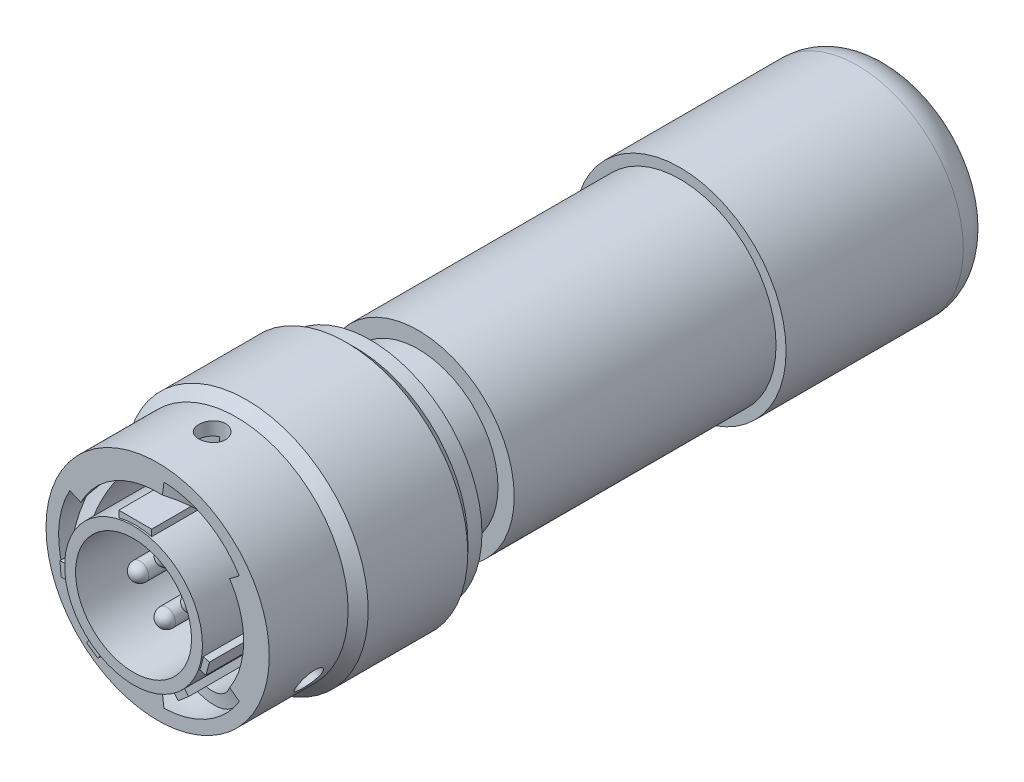
SolidWorks part; units mm, degrees
ref_plane "Front Plane" through (0, 0, 0) normal (0, 0, 1) x (1, 0, 0)
ref_plane "Top Plane" through (0, 0, 0) normal (0, 1, 0) x (1, 0, 0)
ref_plane "Right Plane" through (0, 0, 0) normal (1, 0, 0) x (0, 0, -1)
sketch "Sketch1" plane through (0, 0, 0) normal (1, 0, 0) x (0, 0, -1)
  line L0 (0, 0) -> (68, 0) construction
  line L1 (0, 10.9) -> (0, -10.9) construction
  line L2 (25.5, 8.6) -> (25.5, -8.6) construction
  line L3 (68, 9.5) -> (68, -9.5) construction
  line L4 (0, 7.7089) -> (0, -7.7089) construction
  line L6 (0, 5.1943) -> (0, -5.1943) construction
  line L7 (0, 6.1722) -> (0, -6.1722) construction
  line L8 (7.9502, 5.1435) -> (7.9502, -5.1435) construction
  line L10 (0, 10) -> (0, -10) construction
  line L13 (0, 0) -> (7.9502, 0) construction
  line L14 (32.5, 7.1437) -> (32.5, -7.1437) construction
  line L15 (9.2202, 6.7437) -> (9.2202, -6.7437) construction
  line L16 (0, 8.9154) -> (0, -8.9154) construction
  line L17 (32.5, 7.1437) -> (31.4417, 7.1438) construction
  point P12 (0.1524, 0)
  point P14 (7.9502, 0)
  point P21 (2.159, 0)
  point P22 (5.842, 0)
  point P25 (30.722, 0)
  point P29 (25.5, 0)
  point P30 (23.356, 0)
  point P34 (32.5, 0)
  point P42 (9.2202, 0)
  dimension "D1" = 7.366
  dimension "OAL" = 68
  dimension "D2" = 1.778
  dimension "Q" = 21.8
  dimension "Y" = 12.3444
  dimension "Z" = 10.3886
  dimension "P" = 10.287
  dimension "D" = 2.159
  dimension "W" = 15.4178
  dimension "B-Thread" = 14.2875
  dimension "B-Pitch" = 1.0583
  dimension "L" = 32.5
  dimension "N" = 9.2202
  dimension "X" = 13.4874
  dimension "V" = 17.8308
  dimension "F" = 1.27
  dimension "E" = 3.3782
  dimension "M" = 9.0678
  dimension "Nut OD" = 19
  dimension "Body Lg" = 42.5
  dimension "Body OD" = 17.2
  dimension "Q2" = 20
sketch "Sketch2" plane through (0, 0, 0) normal (0, 0, 1) x (1, 0, 0)
  circle A0 centre (0, 0) radius 6.1722 construction
  circle A1 centre (0, 0) radius 6.7437 construction
  circle A2 centre (0, 0) radius 10.9 construction
  circle A3 centre (0, 0) radius 8.9154 construction
sketch "Sketch3" plane through (0, 0, 0) normal (1, 0, 0) x (0, 0, -1)
  line L0 (0, 0) -> (68, 0) construction
  line L1 (9.7282, 6.7437) -> (9.7282, 6.0854)
  line L2 (0, 6.1722) -> (9.2202, 6.1722)
  line L3 (0, 6.1722) -> (0, 5.1943)
  line L4 (0, 5.1943) -> (32.5, 5.1943)
  line L5 (19.8, 6.0854) -> (20.8583, 7.1438)
  line L6 (9.7282, 6.0854) -> (19.8, 6.0854)
  line L7 (7.9502, 5.1435) -> (30.722, 5.1435)
  line L8 (7.9502, 5.1435) -> (7.9502, 0)
  line L9 (7.9502, 0) -> (30.722, 0)
  line L10 (30.722, 5.1435) -> (30.722, 0)
  line L11 (20.8583, 7.1438) -> (31.4417, 7.1438)
  line L12 (31.4417, 7.1438) -> (32.5, 6.0854)
  line L13 (31.4417, 7.1438) -> (32.5, 7.1437) construction
  line L14 (32.5, 7.1437) -> (32.5, 6.0854) construction
  line L15 (19.8, 6.0854) -> (19.8, 7.1438) construction
  line L16 (19.8, 7.1438) -> (20.8583, 7.1438) construction
  line L26 (32.5, 6.0854) -> (32.5, 5.1943)
  line L31 (9.7282, 6.7437) -> (9.2202, 6.7437)
  line L35 (9.2202, 6.7437) -> (9.2202, 6.1722)
  dimension "D1" = 12.7
  dimension "D2" = 0.508
revolve "Revolve1" add sketch "Sketch3" angle 360 about L0
sketch "Sketch4" plane through (0, 0, 0) normal (0, 0, 1) x (1, 0, 0)
  line L0 (-1.4732, 6.5808) -> (1.4732, 6.5808)
  line L1 (0, 6.5808) -> (0, 0) construction
  line L2 (0, 0) -> (6.4872, -1.7383) construction
  line L3 (0, 0) -> (4.317, -5.1448) construction
  line L4 (0, 0) -> (-3.8522, -5.5015) construction
  line L5 (0, 0) -> (-6.6905, -0.5853) construction
  line L6 (6.645, -1.1494) -> (6.3295, -2.3271)
  line L7 (4.784, -4.753) -> (3.85, -5.5367)
  line L8 (-3.3528, -5.8512) -> (-4.3515, -5.1518)
  line L9 (-6.6374, -1.1926) -> (-6.7437, 0.0219)
  line L10 (6.645, -1.1494) -> (6.0905, -1.0008)
  line L11 (6.3295, -2.3271) -> (5.775, -2.1785)
  line L12 (4.784, -4.753) -> (4.415, -4.3132)
  line L13 (3.85, -5.5367) -> (3.481, -5.0969)
  line L14 (-3.3528, -5.8512) -> (-3.0236, -5.3809)
  line L15 (-4.3515, -5.1518) -> (-4.0223, -4.6816)
  line L16 (-6.6374, -1.1926) -> (-6.0655, -1.1426)
  line L17 (-6.7437, 0.0219) -> (-6.1718, 0.072)
  line L18 (-1.4732, 6.5808) -> (-1.4732, 5.9938)
  line L19 (1.4732, 6.5808) -> (1.4732, 5.9938)
  arc A0 (3.481, -5.0969) -> (4.415, -4.3132) centre (0, 0) ccw
  arc A1 (5.775, -2.1785) -> (6.0905, -1.0008) centre (0, 0) ccw
  circle A2 centre (0, 0) radius 6.1722 construction
  circle A3 centre (0, 0) radius 6.7437 construction
  arc A4 (-4.0223, -4.6816) -> (-3.0236, -5.3809) centre (0, 0) ccw
  circle A5 centre (0, 0) radius 6.7437 construction
  arc A6 (-6.1718, 0.072) -> (-6.0655, -1.1426) centre (0, 0) ccw
  arc A7 (1.4732, 5.9938) -> (-1.4732, 5.9938) centre (0, 0) ccw
  dimension "D1" = 2.9464
  dimension "D2" = 105
  dimension "D3" = 140
  dimension "D4" = 215
  dimension "D5" = 265
  dimension "D6" = 1.2192
extrude "Boss-Extrude1" add sketch "Sketch4" against normal up to vertex (9.2202 mm away) from vertex up to point (0, 0, -9.2202) starting at point (0, 0, -0.1524)
sketch "Sketch5" plane through (0, 0, 0) normal (1, 0, 0) x (0, 0, -1)
  line L0 (32.5, 0) -> (0, 0) construction
  line L1 (2.159, 10) -> (2.159, 7.7089)
  line L3 (17.399, 7.7089) -> (17.399, 8.9789)
  line L4 (17.399, 8.9789) -> (21.209, 8.9789)
  line L5 (21.209, 8.9789) -> (21.209, 10)
  line L6 (2.159, 7.7089) -> (17.399, 7.7089)
  line L7 (2.159, 10) -> (9.2202, 10)
  line L8 (21.209, 10) -> (19.939, 10)
  line L9 (19.939, 10) -> (19.039, 10.9)
  line L10 (19.039, 10.9) -> (10.1202, 10.9)
  line L11 (10.1202, 10.9) -> (9.2202, 10)
  dimension "D2" = 1.27
  dimension "D5" = 45
  dimension "D1" = 3.81
  dimension "D3" = 19.05
  dimension "D4" = 45
  dimension "D6" = 1.27
revolve "Revolve2" add sketch "Sketch5" angle 360 about L0
sketch "Sketch6" plane through (0, 0, 0) normal (0, 1, 0) x (1, 0, 0)
  line L0 (0, 0) -> (0, 68) construction
  circle A0 centre (0, 7.0358) radius 1.1938
  dimension "D1" = 2.3876
extrude "Cut-Extrude1" cut sketch "Sketch6" along normal through all
sketch "Sketch7" plane through (0, 0, -2.159) normal (0, 0, 1) x (1, 0, 0)
  circle A0 centre (0, 0) radius 7.7089 construction
  circle A1 centre (0, 0) radius 7.7089
  point P3 (-7.7089, 0)
curve "Helix/Spiral1" pitch 19.5072 height 4.8768 radius 7.7089 centre (0, 0, -2.159) axis (0, 0, -1) start towards (1, 0, 0)
ref_plane "Plane2" through (-7.7089, 0, -2.159) normal (0, 0.9276, -0.3736) x (-1, 0, 0)
sketch "Sketch8" plane through (-7.7089, 0, -2.159) normal (0, 0.9276, -0.3736) x (-1, 0, 0)
  line L0 (-7.7089, 0) -> (0, 0) construction
  line L1 (0, 0) -> (1.164, 0) construction
  line L2 (-0.1185, 1.3462) -> (1.0613, 1.3462)
  line L3 (1.164, 0) -> (1.164, 2.3275) construction
  line L4 (-0.1185, -1.3462) -> (1.0613, -1.3462)
  arc A0 (1.0613, -1.3462) -> (1.0613, 1.3462) centre (-7.7089, 0) ccw
  arc A1 (-0.1185, -1.3462) -> (-0.1185, 1.3462) centre (-7.7089, 0) ccw
  dimension "GG" = 2.6924
sweep "Cut-Sweep1" cut profiles "Sketch8" path "Helix/Spiral1" align with end faces yes
pattern_circular "CirPattern1" count 3 over 360 about axis through (0, 0, -32.5) along (0, 0, -1) of "Cut-Extrude1", "Cut-Sweep1"
sketch "Sketch9" plane through (0, 0, 0) normal (1, 0, 0) x (0, 0, -1)
  line L0 (25.5, 8.6) -> (25.5, 7.1437)
  line L1 (25.5, 7.1437) -> (64.825, 7.1437)
  line L2 (25.5, 8.6) -> (48.95, 8.6)
  line L3 (48.95, 9.5) -> (48.95, 8.6)
  line L4 (0, 0) -> (68, 0) construction
  line L5 (48.95, 9.5) -> (64.825, 9.5)
  line L6 (68, 3.15) -> (65.6437, 3.15)
  line L7 (65.6437, 3.15) -> (65.6437, 6.325)
  line L9 (68, 3.15) -> (68, 6.325)
  arc A0 (64.825, 9.5) -> (68, 6.325) centre (64.825, 6.325) cw
  arc A1 (65.6437, 6.325) -> (64.825, 7.1437) centre (64.825, 6.325) ccw
  point P11 (68, 9.5)
  dimension "D1" = 3.175
  dimension "D2" = 19.05
  dimension "D3" = 6.35
revolve "Revolve3" add sketch "Sketch9" angle 360 about L4
sketch "Sketch10-xP" plane through (0, 0, -7.9502) normal (0, 0, 1) x (1, 0, 0)
  line L0 (0, 2.3876) -> (0, -2.3876) construction
  line L1 (-2.3876, 0) -> (2.3876, 0) construction
  circle A0 centre (0, 2.3876) radius 0.7938
  circle A1 centre (2.3876, 0) radius 0.7938
  circle A2 centre (0, -2.3876) radius 0.7938
  circle A3 centre (-2.3876, 0) radius 0.7937
  dimension "D1" = 1.5875
  dimension "D2" = 2.3876
  dimension "D3" = 2.3876
extrude "Boss-Extrude10-xP" add sketch "Sketch10-xP" along normal up to vertex (5.7912 mm away) up to point (0, 0, -2.159)
fillet "Fillet10-xP" radius 0.7937 4 edges at (0.7938, 2.3876, -2.159) (-1.5939, 0, -2.159) (0.7938, -2.3876, -2.159) (3.1814, 0, -2.159)
sketch "Sketch10-6P" [suppressed] plane through (0, 0, -7.9502) normal (0, 0, 1) x (1, 0, 0)
  circle A0 centre (0, 3.302) radius 0.508
  circle A1 centre (2.8702, 1.651) radius 0.508
  circle A2 centre (2.8702, -1.651) radius 0.508
  circle A3 centre (0, -3.302) radius 0.508
  circle A4 centre (-2.8702, -1.651) radius 0.508
  circle A5 centre (-2.8702, 1.651) radius 0.508
  dimension "D1" = 1.016
  dimension "D2" = 0
  dimension "D3" = 3.302
  dimension "D4" = 2.8702
  dimension "D5" = 1.651
  dimension "D6" = 2.8702
  dimension "D7" = 1.651
  dimension "D8" = 0
  dimension "D9" = 3.302
  dimension "D10" = 2.8702
  dimension "D11" = 1.651
  dimension "D12" = 2.8702
  dimension "D13" = 1.651
extrude "Boss-Extrude10-6P" [suppressed] add sketch "Sketch10-6P" along normal up to vertex up to point (0, 0, -2.159)
fillet "Fillet10-6P" [suppressed] radius 0.508
equation "\"D3@Helix/Spiral1\" = \"N@Sketch1\" - \"D@Sketch1\" - \"E@Sketch1\" + ( \"D1@Sketch6\" / 2 ) "
equation "\"D1@Fillet10-xP\" = \"D1@Sketch10-xP\" / 2"
equation "\"D1@Fillet10-6P\" = \"D1@Sketch10-6P\" / 2"
